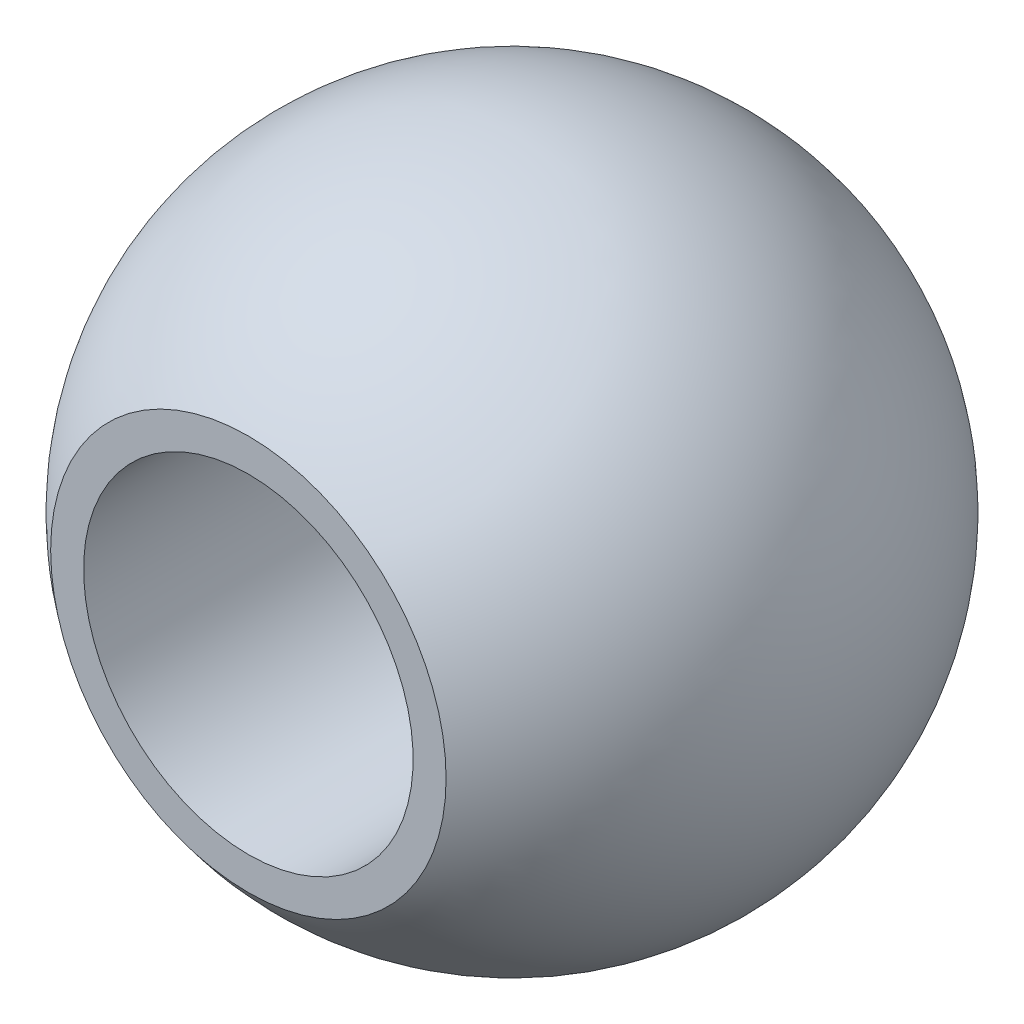
SolidWorks part; units mm, degrees
ref_plane "Płaszczyzna przednia" through (0, 0, 0) normal (0, 0, 1) x (1, 0, 0)
ref_plane "Płaszczyzna górna" through (0, 0, 0) normal (0, 1, 0) x (1, 0, 0)
ref_plane "Płaszczyzna prawa" through (0, 0, 0) normal (1, 0, 0) x (0, 0, -1)
sketch "Szkic1" plane through (0, 0, 0) normal (0, 0, 1) x (1, 0, 0)
  line L0 (0, 6.9744) -> (0, -4.7318) construction
  line L1 (0, 5) -> (0, -5)
  arc A0 (0, 5) -> (0, -5) centre (0, 0) ccw
  dimension "D1" = 10
revolve "Obrót1" add sketch "Szkic1" angle 360 about L0
sketch "Szkic2" plane through (0, 0, 0) normal (0, 0, 1) x (1, 0, 0)
  circle A0 centre (0, 0) radius 2.5
  dimension "D1" = 5
extrude "Wytnij-wyciągnięcie1" cut sketch "Szkic2" against normal blind 10 and the other way blind 10 contours A0
sketch "Szkic3" plane through (0, 0, 0) normal (1, 0, 0) x (0, 0, -1)
  line L0 (0, -5.9943) -> (0, 6.6212) construction
  line L1 (6.4291, -5.9943) -> (4, -5.9943)
  line L2 (-6.4291, 5.3152) -> (-4, 5.3152)
  line L3 (-6.4291, 5.3152) -> (-6.4291, -5.9943)
  line L4 (-6.4291, -5.9943) -> (-4, -5.9943)
  line L5 (-4, 5.3152) -> (-4, -5.9943)
  line L6 (4, 5.3152) -> (4, -5.9943)
  line L7 (6.4291, 5.3152) -> (4, 5.3152)
  line L8 (6.4291, 5.3152) -> (6.4291, -5.9943)
  dimension "D1" = 4
extrude "Wytnij-wyciągnięcie2" cut sketch "Szkic3" against normal blind 10 and the other way blind 10
